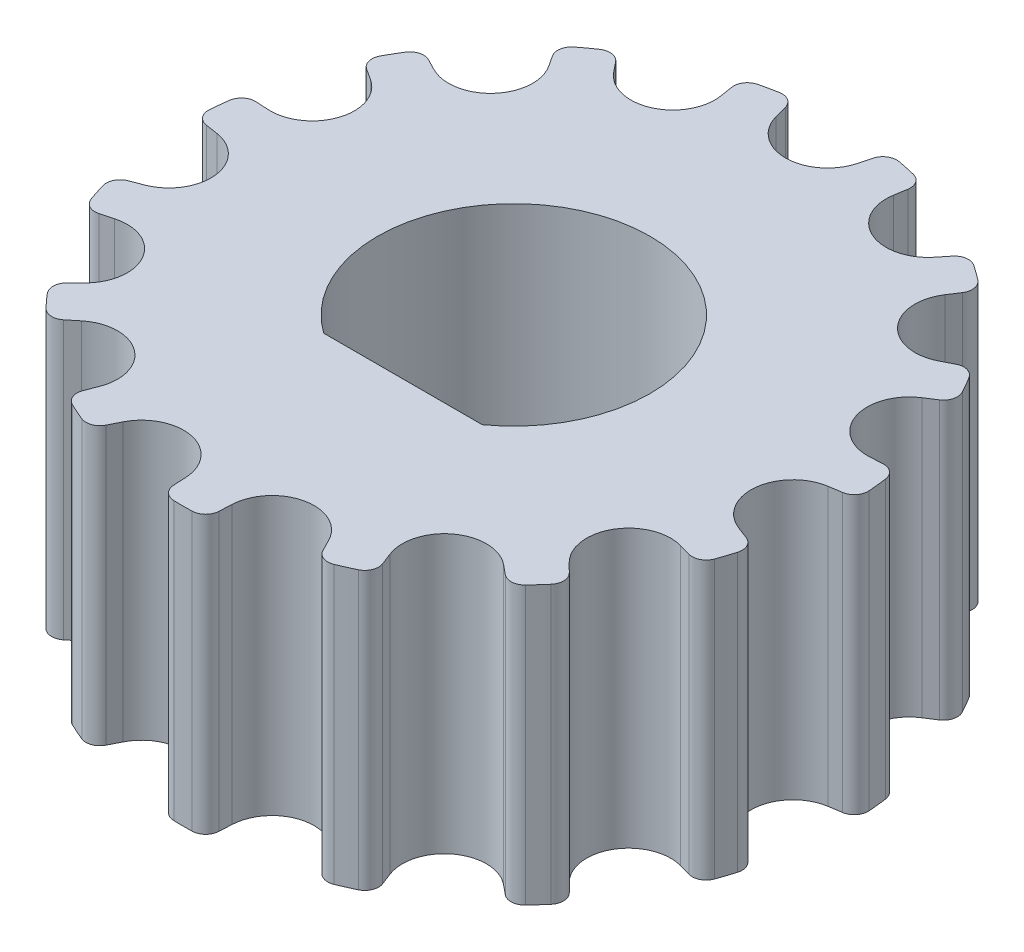
SolidWorks part; units mm, degrees
material "Acrylic (Medium-high impact)"
ref_plane "Front Plane" through (0, 0, 0) normal (0, 0, 1) x (1, 0, 0)
ref_plane "Top Plane" through (0, 0, 0) normal (0, 1, 0) x (1, 0, 0)
ref_plane "Right Plane" through (0, 0, 0) normal (1, 0, 0) x (0, 0, -1)
sketch "Sketch1" plane through (0, 0, 0) normal (0, 1, 0) x (1, 0, 0)
  circle A0 centre (0, 0) radius 7.162
  dimension "D1" = 14.3239
extrude "Boss-Extrude1" add sketch "Sketch1" along normal blind 6
sketch "Sketch2" plane through (0, 6, 0) normal (0, 1, 0) x (1, 0, 0)
  line L0 (0, 0) -> (0, 7.162) construction
  line L1 (-0.8799, 6.5598) -> (-0.95, 6.8255)
  line L2 (-2.913, 6.5428) -> (-2.913, 7.162)
  line L3 (-2.913, 7.162) -> (2.913, 7.162)
  line L4 (0.8799, 6.5598) -> (0.95, 6.8255)
  line L5 (2.913, 6.5428) -> (2.913, 7.162)
  circle A0 centre (0, 0) radius 7.162 construction
  arc A1 (0.8799, 6.5598) -> (-0.8799, 6.5598) centre (0, 6.792) cw
  arc A2 (-0.95, 6.8255) -> (-1.2943, 7.0441) centre (-1.2401, 6.749) ccw
  arc A4 (0.95, 6.8255) -> (1.2943, 7.0441) centre (1.2401, 6.749) cw
  arc A5 (-1.2943, 7.0441) -> (-2.913, 6.5428) centre (0, 0) ccw
  arc A6 (1.2943, 7.0441) -> (2.913, 6.5428) centre (0, 0) cw
  point P11 (0, 7.162)
  point P19 (0, 5.882)
  dimension "D3" = 0.3
  dimension "D5" = 0.91
  dimension "D2" = 0.95
  dimension "D4" = 1.28
  dimension "D6" = 24
extrude "Cut-Extrude1" cut sketch "Sketch2" against normal through all
pattern_circular "CirPattern1" count 15 over 360 about axis through (0, 6, 0) along (0, -1, 0) of "Cut-Extrude1"
sketch "Sketch3" plane through (0, 0, 0) normal (0, -1, 0) x (1, 0, 0)
  line L0 (1.7154, 2.4) -> (-1.7154, 2.4)
  arc A0 (-1.7154, 2.4) -> (1.7154, 2.4) centre (0, 0) ccw
  dimension "D1" = 5.9
  dimension "D2" = 2.4
extrude "Cut-Extrude2" cut sketch "Sketch3" against normal through all
sketch "Sketch5" plane through (0, 0, 0) normal (0, -1, 0) x (1, 0, 0)
  line L60 (5.4179, -3.8244) -> (5.6623, -3.9501)
  line L61 (6.252, -2.9286) -> (6.021, -2.7798)
  line L62 (6.505, -1.2901) -> (6.7794, -1.3055)
  line L63 (6.9027, -0.1325) -> (6.6311, -0.0906)
  line L64 (6.4674, 1.4673) -> (6.7243, 1.5648)
  line L65 (6.3598, 2.6865) -> (6.0946, 2.6144)
  line L66 (5.3115, 3.9709) -> (5.5065, 4.1645)
  line L67 (4.7173, 5.041) -> (4.5044, 4.8673)
  line L68 (3.2371, 5.788) -> (3.3366, 6.0442)
  line L69 (2.2591, 6.5239) -> (2.1352, 6.2786)
  line L70 (0.6031, 6.6042) -> (0.5897, 6.8787)
  line L71 (-0.5897, 6.8787) -> (-0.6031, 6.6042)
  line L72 (-2.1352, 6.2786) -> (-2.2591, 6.5239)
  line L73 (-3.3366, 6.0442) -> (-3.2371, 5.788)
  line L74 (-4.5044, 4.8673) -> (-4.7173, 5.041)
  line L75 (-5.5065, 4.1645) -> (-5.3115, 3.9709)
  line L76 (-6.0946, 2.6144) -> (-6.3598, 2.6865)
  line L77 (-6.7243, 1.5648) -> (-6.4674, 1.4673)
  line L78 (-6.6311, -0.0906) -> (-6.9027, -0.1325)
  line L79 (-6.7794, -1.3055) -> (-6.505, -1.2901)
  line L80 (-6.021, -2.7798) -> (-6.252, -2.9286)
  line L81 (-5.6623, -3.9501) -> (-5.4179, -3.8244)
  line L82 (-4.3698, -4.9885) -> (-4.5203, -5.2184)
  line L83 (-3.5661, -5.9117) -> (-3.394, -5.6974)
  line L84 (-1.963, -6.3345) -> (-2.007, -6.6058)
  line L85 (-0.8533, -6.851) -> (-0.7832, -6.5853)
  line L86 (0.7832, -6.5853) -> (0.8533, -6.851)
  line L87 (2.007, -6.6058) -> (1.963, -6.3345)
  line L88 (3.394, -5.6974) -> (3.5661, -5.9117)
  line L89 (4.5203, -5.2184) -> (4.3698, -4.9885)
  line L90 (5.4179, -3.8244) -> (5.6623, -3.9501)
  line L91 (6.252, -2.9286) -> (6.021, -2.7798)
  line L92 (6.505, -1.2901) -> (6.7794, -1.3055)
  line L93 (6.9027, -0.1325) -> (6.6311, -0.0906)
  line L94 (6.4674, 1.4673) -> (6.7243, 1.5648)
  line L95 (6.3598, 2.6865) -> (6.0946, 2.6144)
  line L96 (5.3115, 3.9709) -> (5.5065, 4.1645)
  line L97 (4.7173, 5.041) -> (4.5044, 4.8673)
  line L98 (3.2371, 5.788) -> (3.3366, 6.0442)
  line L99 (2.2591, 6.5239) -> (2.1352, 6.2786)
  line L100 (0.6031, 6.6042) -> (0.5897, 6.8787)
  line L101 (-0.5897, 6.8787) -> (-0.6031, 6.6042)
  line L102 (-2.1352, 6.2786) -> (-2.2591, 6.5239)
  line L103 (-3.3366, 6.0442) -> (-3.2371, 5.788)
  line L104 (-4.5044, 4.8673) -> (-4.7173, 5.041)
  line L105 (-5.5065, 4.1645) -> (-5.3115, 3.9709)
  line L106 (-6.0946, 2.6144) -> (-6.3598, 2.6865)
  line L107 (-6.7243, 1.5648) -> (-6.4674, 1.4673)
  line L108 (-6.6311, -0.0906) -> (-6.9027, -0.1325)
  line L109 (-6.7794, -1.3055) -> (-6.505, -1.2901)
  line L110 (-6.021, -2.7798) -> (-6.252, -2.9286)
  line L111 (-5.6623, -3.9501) -> (-5.4179, -3.8244)
  line L112 (-4.3698, -4.9885) -> (-4.5203, -5.2184)
  line L113 (-3.5661, -5.9117) -> (-3.394, -5.6974)
  line L114 (-1.963, -6.3345) -> (-2.007, -6.6058)
  line L115 (-0.8533, -6.851) -> (-0.7832, -6.5853)
  line L116 (0.7832, -6.5853) -> (0.8533, -6.851)
  line L117 (2.007, -6.6058) -> (1.963, -6.3345)
  line L118 (3.394, -5.6974) -> (3.5661, -5.9117)
  line L119 (4.5203, -5.2184) -> (4.3698, -4.9885)
  circle A60 centre (0, 0) radius 3.9038
  arc A120 (5.6623, -3.9501) -> (6.186, -3.8039) centre (5.8452, -3.5944) ccw
  arc A121 (6.186, -3.8039) -> (6.3873, -3.4553) centre (0, 0) ccw
  arc A122 (6.3873, -3.4553) -> (6.252, -2.9286) centre (6.0355, -3.2649) ccw
  arc A123 (6.505, -1.2901) -> (6.021, -2.7798) centre (6.4595, -2.0988) ccw
  arc A124 (6.7794, -1.3055) -> (7.1984, -0.959) centre (6.8019, -0.9062) ccw
  arc A125 (7.1984, -0.959) -> (7.2405, -0.5586) centre (0, 0) ccw
  arc A126 (7.2405, -0.5586) -> (6.9027, -0.1325) centre (6.8416, -0.5278) ccw
  arc A127 (6.4674, 1.4673) -> (6.6311, -0.0906) centre (6.7548, 0.71) ccw
  arc A128 (6.7243, 1.5648) -> (6.9661, 2.0518) centre (6.5824, 1.9387) ccw
  arc A129 (6.9661, 2.0518) -> (6.8417, 2.4347) centre (0, 0) ccw
  arc A130 (6.8417, 2.4347) -> (6.3598, 2.6865) centre (6.4648, 2.3006) ccw
  arc A131 (5.3115, 3.9709) -> (6.0946, 2.6144) centre (5.882, 3.396) ccw
  arc A132 (5.5065, 4.1645) -> (5.5293, 4.7077) centre (5.2248, 4.4484) ccw
  arc A133 (5.5293, 4.7077) -> (5.2599, 5.0069) centre (0, 0) ccw
  arc A134 (5.2599, 5.0069) -> (4.7173, 5.041) centre (4.9702, 4.7312) ccw
  arc A135 (3.2371, 5.788) -> (4.5044, 4.8673) centre (3.9922, 5.4948) ccw
  arc A136 (3.3366, 6.0442) -> (3.1365, 6.5497) centre (2.9637, 6.1889) ccw
  arc A137 (3.1365, 6.5497) -> (2.7687, 6.7135) centre (0, 0) ccw
  arc A138 (2.7687, 6.7135) -> (2.2591, 6.5239) centre (2.6162, 6.3437) ccw
  arc A139 (0.6031, 6.6042) -> (2.1352, 6.2786) centre (1.4121, 6.6436) ccw
  arc A140 (0.5897, 6.8787) -> (0.2013, 7.2592) centre (0.1902, 6.8593) ccw
  arc A141 (0.2013, 7.2592) -> (-0.2013, 7.2592) centre (0, 0) ccw
  arc A142 (-0.2013, 7.2592) -> (-0.5897, 6.8787) centre (-0.1902, 6.8593) ccw
  arc A143 (-2.1352, 6.2786) -> (-0.6031, 6.6042) centre (-1.4121, 6.6436) ccw
  arc A144 (-2.2591, 6.5239) -> (-2.7687, 6.7135) centre (-2.6162, 6.3437) ccw
  arc A145 (-2.7687, 6.7135) -> (-3.1365, 6.5497) centre (0, 0) ccw
  arc A146 (-3.1365, 6.5497) -> (-3.3366, 6.0442) centre (-2.9637, 6.1889) ccw
  arc A147 (-4.5044, 4.8673) -> (-3.2371, 5.788) centre (-3.9922, 5.4948) ccw
  arc A148 (-4.7173, 5.041) -> (-5.2599, 5.0069) centre (-4.9702, 4.7312) ccw
  arc A149 (-5.2599, 5.0069) -> (-5.5293, 4.7077) centre (0, 0) ccw
  arc A150 (-5.5293, 4.7077) -> (-5.5065, 4.1645) centre (-5.2248, 4.4484) ccw
  arc A151 (-6.0946, 2.6144) -> (-5.3115, 3.9709) centre (-5.882, 3.396) ccw
  arc A152 (-6.3598, 2.6865) -> (-6.8417, 2.4347) centre (-6.4648, 2.3006) ccw
  arc A153 (-6.8417, 2.4347) -> (-6.9661, 2.0518) centre (0, 0) ccw
  arc A154 (-6.9661, 2.0518) -> (-6.7243, 1.5648) centre (-6.5824, 1.9387) ccw
  arc A155 (-6.6311, -0.0906) -> (-6.4674, 1.4673) centre (-6.7548, 0.71) ccw
  arc A156 (-6.9027, -0.1325) -> (-7.2405, -0.5586) centre (-6.8416, -0.5278) ccw
  arc A157 (-7.2405, -0.5586) -> (-7.1984, -0.959) centre (0, 0) ccw
  arc A158 (-7.1984, -0.959) -> (-6.7794, -1.3055) centre (-6.8019, -0.9062) ccw
  arc A159 (-6.021, -2.7798) -> (-6.505, -1.2901) centre (-6.4595, -2.0988) ccw
  arc A160 (-6.252, -2.9286) -> (-6.3873, -3.4553) centre (-6.0355, -3.2649) ccw
  arc A161 (-6.3873, -3.4553) -> (-6.186, -3.8039) centre (0, 0) ccw
  arc A162 (-6.186, -3.8039) -> (-5.6623, -3.9501) centre (-5.8452, -3.5944) ccw
  arc A163 (-4.3698, -4.9885) -> (-5.4179, -3.8244) centre (-5.0474, -4.5447) ccw
  arc A164 (-4.5203, -5.2184) -> (-4.4297, -5.7545) centre (-4.1857, -5.4375) ccw
  arc A165 (-4.4297, -5.7545) -> (-4.104, -5.9911) centre (0, 0) ccw
  arc A166 (-4.104, -5.9911) -> (-3.5661, -5.9117) centre (-3.8779, -5.6611) ccw
  arc A167 (-1.963, -6.3345) -> (-3.394, -5.6974) centre (-2.7625, -6.2048) ccw
  arc A168 (-2.007, -6.6058) -> (-1.7062, -7.0587) centre (-1.6122, -6.6699) ccw
  arc A169 (-1.7062, -7.0587) -> (-1.3124, -7.1424) centre (0, 0) ccw
  arc A170 (-1.3124, -7.1424) -> (-0.8533, -6.851) centre (-1.2401, -6.749) ccw
  arc A171 (0.7832, -6.5853) -> (-0.7832, -6.5853) centre (0, -6.792) ccw
  arc A172 (0.8533, -6.851) -> (1.3124, -7.1424) centre (1.2401, -6.749) ccw
  arc A173 (1.3124, -7.1424) -> (1.7062, -7.0587) centre (0, 0) ccw
  arc A174 (1.7062, -7.0587) -> (2.007, -6.6058) centre (1.6122, -6.6699) ccw
  arc A175 (3.394, -5.6974) -> (1.963, -6.3345) centre (2.7625, -6.2048) ccw
  arc A176 (3.5661, -5.9117) -> (4.104, -5.9911) centre (3.8779, -5.6611) ccw
  arc A177 (4.104, -5.9911) -> (4.4297, -5.7545) centre (0, 0) ccw
  arc A178 (4.4297, -5.7545) -> (4.5203, -5.2184) centre (4.1857, -5.4375) ccw
  arc A179 (5.4179, -3.8244) -> (4.3698, -4.9885) centre (5.0474, -4.5447) ccw
  arc A180 (5.6623, -3.9501) -> (6.186, -3.8039) centre (5.8452, -3.5944) ccw
  arc A181 (6.186, -3.8039) -> (6.3873, -3.4553) centre (0, 0) ccw
  arc A182 (6.3873, -3.4553) -> (6.252, -2.9286) centre (6.0355, -3.2649) ccw
  arc A183 (6.505, -1.2901) -> (6.021, -2.7798) centre (6.4595, -2.0988) ccw
  arc A184 (6.7794, -1.3055) -> (7.1984, -0.959) centre (6.8019, -0.9062) ccw
  arc A185 (7.1984, -0.959) -> (7.2405, -0.5586) centre (0, 0) ccw
  arc A186 (7.2405, -0.5586) -> (6.9027, -0.1325) centre (6.8416, -0.5278) ccw
  arc A187 (6.4674, 1.4673) -> (6.6311, -0.0906) centre (6.7548, 0.71) ccw
  arc A188 (6.7243, 1.5648) -> (6.9661, 2.0518) centre (6.5824, 1.9387) ccw
  arc A189 (6.9661, 2.0518) -> (6.8417, 2.4347) centre (0, 0) ccw
  arc A190 (6.8417, 2.4347) -> (6.3598, 2.6865) centre (6.4648, 2.3006) ccw
  arc A191 (5.3115, 3.9709) -> (6.0946, 2.6144) centre (5.882, 3.396) ccw
  arc A192 (5.5065, 4.1645) -> (5.5293, 4.7077) centre (5.2248, 4.4484) ccw
  arc A193 (5.5293, 4.7077) -> (5.2599, 5.0069) centre (0, 0) ccw
  arc A194 (5.2599, 5.0069) -> (4.7173, 5.041) centre (4.9702, 4.7312) ccw
  arc A195 (3.2371, 5.788) -> (4.5044, 4.8673) centre (3.9922, 5.4948) ccw
  arc A196 (3.3366, 6.0442) -> (3.1365, 6.5497) centre (2.9637, 6.1889) ccw
  arc A197 (3.1365, 6.5497) -> (2.7687, 6.7135) centre (0, 0) ccw
  arc A198 (2.7687, 6.7135) -> (2.2591, 6.5239) centre (2.6162, 6.3437) ccw
  arc A199 (0.6031, 6.6042) -> (2.1352, 6.2786) centre (1.4121, 6.6436) ccw
  arc A200 (0.5897, 6.8787) -> (0.2013, 7.2592) centre (0.1902, 6.8593) ccw
  arc A201 (0.2013, 7.2592) -> (-0.2013, 7.2592) centre (0, 0) ccw
  arc A202 (-0.2013, 7.2592) -> (-0.5897, 6.8787) centre (-0.1902, 6.8593) ccw
  arc A203 (-2.1352, 6.2786) -> (-0.6031, 6.6042) centre (-1.4121, 6.6436) ccw
  arc A204 (-2.2591, 6.5239) -> (-2.7687, 6.7135) centre (-2.6162, 6.3437) ccw
  arc A205 (-2.7687, 6.7135) -> (-3.1365, 6.5497) centre (0, 0) ccw
  arc A206 (-3.1365, 6.5497) -> (-3.3366, 6.0442) centre (-2.9637, 6.1889) ccw
  arc A207 (-4.5044, 4.8673) -> (-3.2371, 5.788) centre (-3.9922, 5.4948) ccw
  arc A208 (-4.7173, 5.041) -> (-5.2599, 5.0069) centre (-4.9702, 4.7312) ccw
  arc A209 (-5.2599, 5.0069) -> (-5.5293, 4.7077) centre (0, 0) ccw
  arc A210 (-5.5293, 4.7077) -> (-5.5065, 4.1645) centre (-5.2248, 4.4484) ccw
  arc A211 (-6.0946, 2.6144) -> (-5.3115, 3.9709) centre (-5.882, 3.396) ccw
  arc A212 (-6.3598, 2.6865) -> (-6.8417, 2.4347) centre (-6.4648, 2.3006) ccw
  arc A213 (-6.8417, 2.4347) -> (-6.9661, 2.0518) centre (0, 0) ccw
  arc A214 (-6.9661, 2.0518) -> (-6.7243, 1.5648) centre (-6.5824, 1.9387) ccw
  arc A215 (-6.6311, -0.0906) -> (-6.4674, 1.4673) centre (-6.7548, 0.71) ccw
  arc A216 (-6.9027, -0.1325) -> (-7.2405, -0.5586) centre (-6.8416, -0.5278) ccw
  arc A217 (-7.2405, -0.5586) -> (-7.1984, -0.959) centre (0, 0) ccw
  arc A218 (-7.1984, -0.959) -> (-6.7794, -1.3055) centre (-6.8019, -0.9062) ccw
  arc A219 (-6.021, -2.7798) -> (-6.505, -1.2901) centre (-6.4595, -2.0988) ccw
  arc A220 (-6.252, -2.9286) -> (-6.3873, -3.4553) centre (-6.0355, -3.2649) ccw
  arc A221 (-6.3873, -3.4553) -> (-6.186, -3.8039) centre (0, 0) ccw
  arc A222 (-6.186, -3.8039) -> (-5.6623, -3.9501) centre (-5.8452, -3.5944) ccw
  arc A223 (-4.3698, -4.9885) -> (-5.4179, -3.8244) centre (-5.0474, -4.5447) ccw
  arc A224 (-4.5203, -5.2184) -> (-4.4297, -5.7545) centre (-4.1857, -5.4375) ccw
  arc A225 (-4.4297, -5.7545) -> (-4.104, -5.9911) centre (0, 0) ccw
  arc A226 (-4.104, -5.9911) -> (-3.5661, -5.9117) centre (-3.8779, -5.6611) ccw
  arc A227 (-1.963, -6.3345) -> (-3.394, -5.6974) centre (-2.7625, -6.2048) ccw
  arc A228 (-2.007, -6.6058) -> (-1.7062, -7.0587) centre (-1.6122, -6.6699) ccw
  arc A229 (-1.7062, -7.0587) -> (-1.3124, -7.1424) centre (0, 0) ccw
  arc A230 (-1.3124, -7.1424) -> (-0.8533, -6.851) centre (-1.2401, -6.749) ccw
  arc A231 (0.7832, -6.5853) -> (-0.7832, -6.5853) centre (0, -6.792) ccw
  arc A232 (0.8533, -6.851) -> (1.3124, -7.1424) centre (1.2401, -6.749) ccw
  arc A233 (1.3124, -7.1424) -> (1.7062, -7.0587) centre (0, 0) ccw
  arc A234 (1.7062, -7.0587) -> (2.007, -6.6058) centre (1.6122, -6.6699) ccw
  arc A235 (3.394, -5.6974) -> (1.963, -6.3345) centre (2.7625, -6.2048) ccw
  arc A236 (3.5661, -5.9117) -> (4.104, -5.9911) centre (3.8779, -5.6611) ccw
  arc A237 (4.104, -5.9911) -> (4.4297, -5.7545) centre (0, 0) ccw
  arc A238 (4.4297, -5.7545) -> (4.5203, -5.2184) centre (4.1857, -5.4375) ccw
  arc A239 (5.4179, -3.8244) -> (4.3698, -4.9885) centre (5.0474, -4.5447) ccw
  dimension "D1" = 0.1
extrude "Boss-Extrude2" [suppressed] add sketch "Sketch5" against normal up to surface (5.8 mm away) up to face at (0, 6, -0.275)
sketch "Sketch6" plane through (0, 6, 0) normal (0, 1, 0) x (1, 0, 0)
  circle A0 centre (0, -10) radius 2.5
  dimension "D1" = 5
  dimension "D2" = 10
extrude "Cut-Extrude3" [suppressed] cut sketch "Sketch6" against normal through all
equation "\"smallPulleyTeeth\"= 15"
equation "\"largePulleyTeeth\"= 30"
equation "\"eighthThick\"= 3.0mm"
equation "\"D1@Sketch1\"=3*\"smallPulleyTeeth\"/pi"
equation "\"D1@Boss-Extrude1\" = \"eighthThick\" * 2"
equation "\"D6@Sketch2\"=360/\"smallPulleyTeeth\""
equation "\"quarterThick\"=6.0mm"
equation "\"D1@CirPattern1\"=\"smallPulleyTeeth\""
equation "\"sixteenthThick\"= 1.7mm"
equation "\"OD\"= 145mm"
equation "\"puckAngle\"= 60.5deg"
equation "\"puckDiam\"= 76.5mm"
equation "\"axlePress\"= 5.9mm"
equation "\"press\"= 0.2mm"
equation "\"wheelClear\"= 0.3mm"
equation "\"10-32clear\"= 4.8mm"
equation "\"6-32clear\"= 3.3mm"
equation "\"8-32clear\"= 4.0mm"
equation "\"wheelHeight\"= 22mm"
equation "\"D1@Sketch3\"=\"axlePress\""
